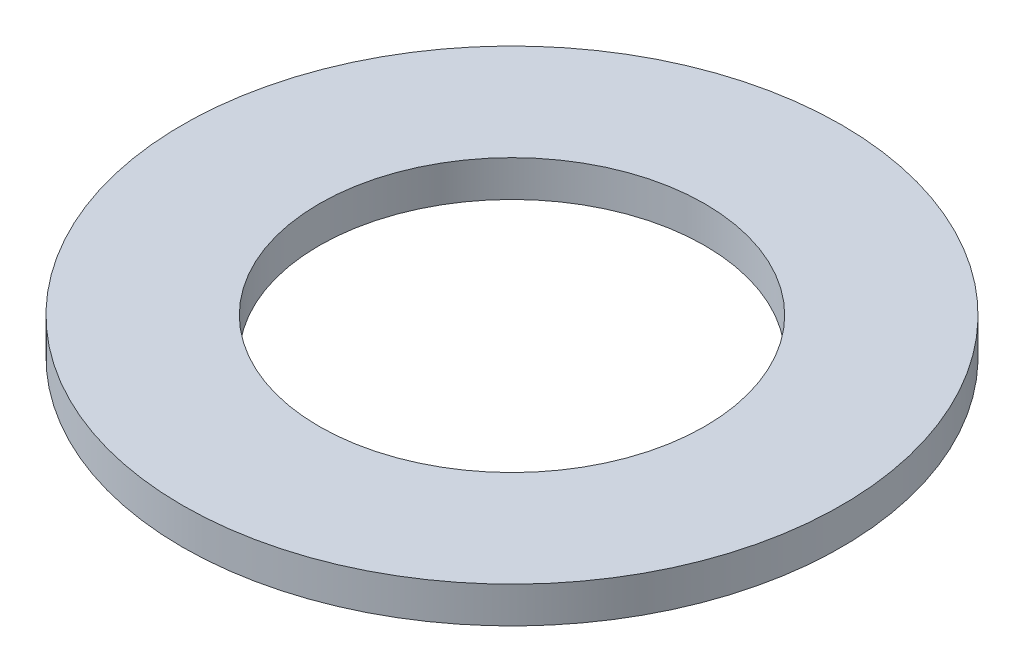
SolidWorks part; units mm, degrees
material "Teak"
ref_plane "Front Plane" through (0, 0, 0) normal (0, 0, 1) x (1, 0, 0)
ref_plane "Top Plane" through (0, 0, 0) normal (0, 1, 0) x (1, 0, 0)
ref_plane "Right Plane" through (0, 0, 0) normal (1, 0, 0) x (0, 0, -1)
sketch "Sketch1" plane through (0, 0, 0) normal (0, 1, 0) x (1, 0, 0)
  circle A0 centre (0, 0) radius 15.975
  circle A1 centre (0, 0) radius 27.3
  dimension "D1" = 54.6
  dimension "D2" = 31.95
extrude "Boss-Extrude1" add sketch "Sketch1" along normal blind 3
